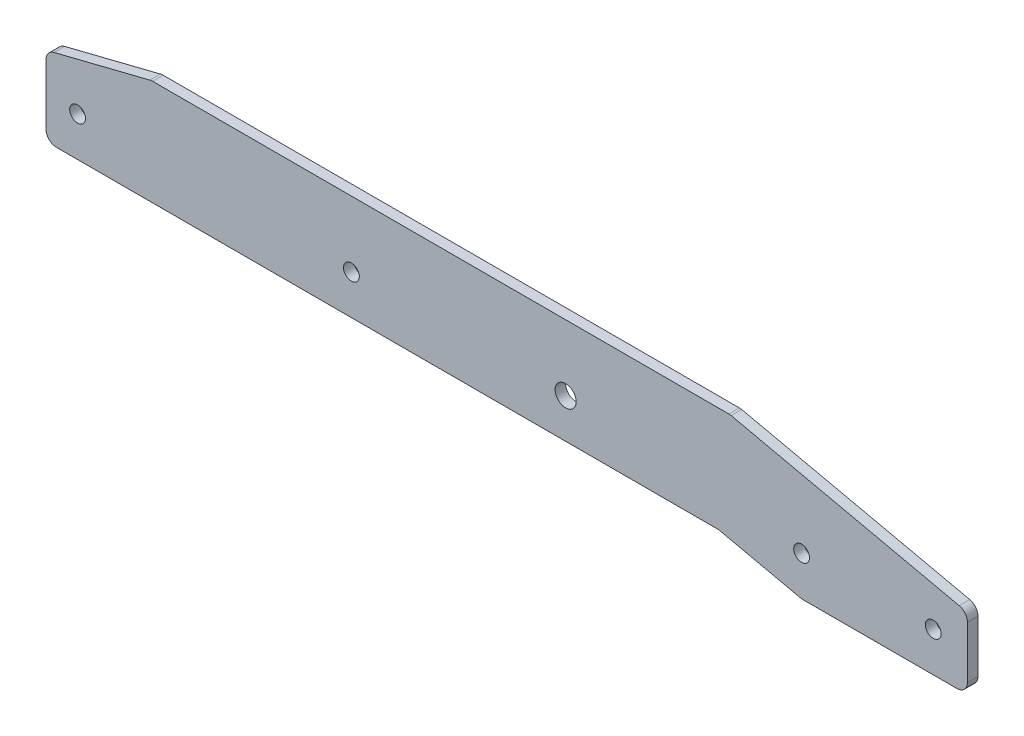
SolidWorks part; units mm, degrees
ref_plane "Спереди" through (0, 0, 0) normal (0, 0, 1) x (1, 0, 0)
ref_plane "Сверху" through (0, 0, 0) normal (0, 1, 0) x (1, 0, 0)
ref_plane "Справа" through (0, 0, 0) normal (1, 0, 0) x (0, 0, -1)
sketch "эскиз" plane through (0, 0, 0) normal (0, 0, 1) x (1, 0, 0)
  line L0 (116.6288, -120) -> (116.6288, -34) construction
  line L1 (-31.3712, -120) -> (-31.3712, -37.5) construction
  line L2 (-163.3712, -34) -> (-129.3712, -34) construction
  line L3 (-163.3712, -120) -> (-31.3712, -120) construction
  line L4 (-163.3712, -34) -> (-181.3712, -34) construction
  line L5 (-31.3712, -120) -> (116.6288, -120) construction
  line L6 (-163.3712, -120) -> (-163.3712, -34) construction
  line L7 (82.6288, -34) -> (116.6288, -34) construction
  line L8 (134.6288, -34) -> (116.6288, -34) construction
  line L9 (-43.8712, -37.5) -> (-18.8712, -37.5) construction
  line L10 (-163.3712, -34) -> (-88.6867, -34) construction
  line L11 (-88.6867, -34) -> (-31.3712, -37.5) construction
  line L12 (-88.6867, -34) -> (0, 0) construction
  line L13 (0, 0) -> (116.6288, -34) construction
  line L14 (-88.6867, -34) -> (-88.6867, 2) construction
  circle A0 centre (-163.3712, -120) radius 57.5 construction
  circle A1 centre (-31.3712, -120) radius 57.5 construction
  circle A2 centre (116.6288, -120) radius 57.5 construction
  circle A3 centre (-181.3712, -34) radius 1.5 construction
  circle A4 centre (-129.3712, -34) radius 1.5 construction
  circle A5 centre (82.6288, -34) radius 1.5 construction
  circle A6 centre (134.6288, -34) radius 1.5 construction
  circle A7 centre (-43.8712, -37.5) radius 1.5 construction
  circle A8 centre (-18.8712, -37.5) radius 1.5 construction
  circle A9 centre (-88.6867, -3) radius 1.5
  circle A10 centre (-88.6867, -13) radius 1.5
  point P31 (-146.3712, -34)
  dimension "D1" = 115
  dimension "D4" = 3
  dimension "D7" = 25
  dimension "D12" = 3
  dimension "D2" = 132
  dimension "D3" = 86
  dimension "D5" = 18
  dimension "D6" = 34
  dimension "D9" = 280
  dimension "D10" = 82.5
  dimension "D11" = 36
  dimension "D13" = 10
  dimension "D14" = 5
  dimension "D15" = 120
sketch "эскиз 1" plane through (0, 0, 0) normal (0, 0, 1) x (1, 0, 0)
  line L0 (-187.3712, -21.5) -> (-187.3712, -41.5)
  line L1 (-187.3712, -41.5) -> (-108.8339, -41.5)
  line L2 (-108.8339, -41.5) -> (-59.6529, -41.5)
  line L3 (-59.6529, -41.5) -> (-43.8712, -45)
  line L4 (-43.8712, -45) -> (-12.3712, -45)
  line L5 (-12.3712, -45) -> (-12.3712, -31.5)
  line L6 (-163.3712, -34) -> (-88.6867, -34) construction
  line L7 (-12.3712, -31.5) -> (-57.4618, -21.5)
  line L8 (-57.4618, -21.5) -> (-110.0582, -21.5)
  line L9 (-110.0582, -21.5) -> (-187.3712, -21.5)
  line L10 (-12.3712, -35) -> (-55.1438, -35) construction
  line L11 (-187.3712, -34) -> (-129.3712, -34) construction
  line L12 (-129.3712, -34) -> (-70.9255, -31.5) construction
  line L13 (-70.9255, -31.5) -> (-43.8712, -37.5) construction
  line L14 (-43.8712, -37.5) -> (-5.3712, -37.5) construction
  line L15 (-163.3712, -34) -> (-129.3712, -34) construction
  line L16 (-43.8712, -37.5) -> (-18.8712, -37.5) construction
  line L17 (-163.3712, -120) -> (-163.3712, -34) construction
  line L20 (-187.3712, -31.5) -> (-109.029, -31.5) construction
  dimension "D1" = 24
  dimension "D2" = 7.5
  dimension "D3" = 20
  dimension "D4" = 19
  dimension "D5" = 20
  dimension "D6" = 2.5
  dimension "D7" = 2.5
  dimension "D8" = 10
extrude "тело маленькой арки" add sketch "эскиз 1" along normal blind 2
sketch "Эскиз1" [suppressed] plane through (0, 0, 0) normal (0, 0, 1) x (1, 0, 0)
  line L0 (40, 10) -> (83.152, -21.5)
  line L1 (83.152, -21.5) -> (141.6288, -21.5)
  line L2 (141.6288, -21.5) -> (141.6288, -41.5)
  line L3 (141.6288, -41.5) -> (76.6288, -41.5)
  line L4 (76.6288, -41.5) -> (33.4768, -10)
  line L5 (33.4768, -10) -> (-10, -10)
  line L6 (-97.6867, -10) -> (-97.6867, 10)
  line L7 (-10, -10) -> (-10, 29.5)
  line L8 (-97.6867, 0) -> (0, 0) construction
  line L9 (0, 0) -> (46.5768, -34) construction
  line L10 (46.5768, -34) -> (141.6288, -34) construction
  line L11 (116.6288, -120) -> (116.6288, -34) construction
  line L12 (82.6288, -34) -> (116.6288, -34) construction
  line L13 (141.6288, -31.5) -> (43.152, -31.5) construction
  line L14 (134.6288, -34) -> (116.6288, -34) construction
  line L15 (-97.6867, -10) -> (-97.6867, -18)
  line L16 (-97.6867, -18) -> (-79.6867, -18)
  line L17 (-79.6867, -18) -> (-79.6867, -0.2843)
  line L18 (-88.6867, 4.8579) -> (-88.6867, -18) construction
  line L19 (-88.6867, -34) -> (-88.6867, 2) construction
  line L20 (0, 0) -> (0, 39.5) construction
  line L21 (-10, 29.5) -> (-49.9025, 29.5)
  line L22 (-49.9025, 29.5) -> (-79.6867, -0.2843)
  line L23 (40, 10) -> (10, 10)
  line L24 (10, 10) -> (10, 49.5)
  line L25 (10, 49.5) -> (-58.1867, 49.5)
  line L26 (-58.1867, 49.5) -> (-97.6867, 10)
  line L27 (0, 39.5) -> (-54.0446, 39.5) construction
  line L28 (-54.0446, 39.5) -> (-88.6867, 4.8579) construction
  point P29 (-88.6867, -18)
  dimension "D1" = 20
  dimension "D2" = 25
  dimension "D3" = 40
  dimension "D4" = 20
  dimension "D5" = 10
  dimension "D6" = 2.5
  dimension "D7" = 88.6867
  dimension "D8" = 9
  dimension "D9" = 5
  dimension "D10" = 39.5
  dimension "D11" = 10
  dimension "D12" = 10
  dimension "D13" = 10
  dimension "D14" = 10
  dimension "D15" = 135
  dimension "D16" = 10
  dimension "D17" = 20
  dimension "D18" = 30
extrude "тело большой арки" [suppressed] add sketch "Эскиз1" along normal blind 2
sketch "Эскиз2" plane through (0, 0, 2) normal (0, 0, 1) x (1, 0, 0)
  circle A0 centre (-181.3712, -34) radius 1.5
  circle A1 centre (-129.3712, -34) radius 1.5
  dimension "D1" = 3
extrude "крепление сервы" cut sketch "Эскиз2" against normal through all
sketch "Эскиз3" plane through (0, 0, 2) normal (0, 0, 1) x (1, 0, 0)
  circle A0 centre (-43.8712, -37.5) radius 1.5
  circle A1 centre (-18.8712, -37.5) radius 1.5
  dimension "D1" = 3
extrude "крепление неподвижного колеса" cut sketch "Эскиз3" against normal through all
sketch "Эскиз4" plane through (0, 0, 2) normal (0, 0, 1) x (1, 0, 0)
  circle A0 centre (-88.6867, -34) radius 2
  dimension "D1" = 4
extrude "ось вращения маленькой арки" cut sketch "Эскиз4" against normal through all
sketch "Эскиз5" [suppressed] plane through (0, 0, 2) normal (0, 0, 1) x (1, 0, 0)
  circle A0 centre (82.6288, -34) radius 1.5
  circle A1 centre (134.6288, -34) radius 1.5
  dimension "D1" = 3
extrude "крепление сервы к большой арке" [suppressed] cut sketch "Эскиз5" against normal through all
sketch "Эскиз6" [suppressed] plane through (0, 0, 2) normal (0, 0, 1) x (1, 0, 0)
  circle A0 centre (0, 0) radius 5.5
  dimension "D1" = 11
extrude "ось вращения большой арки" [suppressed] cut sketch "Эскиз6" against normal through all
sketch "Эскиз9" [suppressed] plane through (0, 0, 2) normal (0, 0, 1) x (1, 0, 0)
  circle A0 centre (-88.6867, -3) radius 1.5
  circle A1 centre (-88.6867, -13) radius 1.5
  dimension "D1" = 3
extrude "крепление к маленькой арке" [suppressed] cut sketch "Эскиз9" against normal through all
sketch "Эскиз13" [suppressed] plane through (0, 0, 2) normal (0, 0, 1) x (1, 0, 0)
  line L0 (33.4768, -10) -> (40, 10) construction
  line L1 (83.152, -21.5) -> (71.36, -37.6539) construction
  line L3 (33.4768, -10) -> (76.6288, -41.5) construction
  line L5 (83.152, -21.5) -> (40, 10) construction
  line L8 (77.256, -29.577) -> (36.7384, 0) construction
  line L9 (36.7384, 0) -> (0, 0) construction
  line L10 (20.9607, 0) -> (49.482, -9.3025) construction
  circle A0 centre (20.9607, 0) radius 1.5
  circle A1 centre (49.482, -9.3025) radius 1.5
  point P15 (35.2213, -4.6513)
  dimension "D1" = 3
  dimension "D2" = 30
extrude "отверстия для ребра сзади" [suppressed] cut sketch "Эскиз13" against normal through all
sketch "Эскиз14" [suppressed] plane through (0, 0, 2) normal (0, 0, 1) x (1, 0, 0)
  line L2 (0, 39.5) -> (0, 0) construction
  circle A0 centre (0, 39.5) radius 2
  dimension "D1" = 4
  dimension "D2" = 39.5
extrude "отверстие для тяга" [suppressed] cut sketch "Эскиз14" against normal through all
sketch "Эскиз18" [suppressed] plane through (0, 0, 2) normal (0, 0, 1) x (1, 0, 0)
  line L0 (-79.6867, -0.2843) -> (-93.8289, 13.8579) construction
  line L1 (-58.1867, 49.5) -> (-97.6867, 10) construction
  line L4 (-79.6867, -0.2843) -> (-49.9025, 29.5) construction
  line L5 (-49.9025, 29.5) -> (-58.1867, 49.5) construction
  line L6 (-10, 29.5) -> (-10, 49.5) construction
  line L7 (10, 49.5) -> (-58.1867, 49.5) construction
  line L8 (-86.7578, 6.7868) -> (-54.0446, 39.5) construction
  line L9 (-54.0446, 39.5) -> (-10, 39.5) construction
  line L10 (-65.5251, 28.0195) -> (-37.8087, 39.5) construction
  circle A0 centre (-37.8087, 39.5) radius 1.5
  circle A1 centre (-65.5251, 28.0195) radius 1.5
  point P22 (-51.6669, 33.7597)
  dimension "D1" = 3
  dimension "D2" = 30
extrude "отверстия для ребра спереди" [suppressed] cut sketch "Эскиз18" against normal through all
sketch "Эскиз16" [suppressed] plane through (0, 0, 2) normal (0, 0, 1) x (1, 0, 0)
  line L0 (0, 0) -> (-8.6933, 2.3294) construction
  line L1 (0, 0) -> (6.364, 6.364) construction
  line L2 (2.3294, -8.6933) -> (0, 0) construction
  line L3 (-88.6867, -3) -> (-88.6867, -13) construction
  line L4 (-10, 29.5) -> (-10, -10) construction
  circle A0 centre (0, 0) radius 9 construction
  circle A1 centre (-8.6933, 2.3294) radius 1.5
  circle A2 centre (6.364, 6.364) radius 1.5
  circle A3 centre (0, 0) radius 5.5
  circle A4 centre (2.3294, -8.6933) radius 1.5
  dimension "D1" = 18
  dimension "D2" = 3
  dimension "D4" = 120
  dimension "D3" = 11
  dimension "D5" = 45
  dimension "D6" = 120
extrude "крепление большой арки" [suppressed] cut sketch "Эскиз16" against normal through all
sketch "Эскиз19" [suppressed] plane through (0, 0, 2) normal (0, 0, 1) x (1, 0, 0)
  circle A0 centre (-8.6933, 2.3294) radius 1.5
  circle A1 centre (-8.6933, 2.3294) radius 3.5
  circle A2 centre (2.3294, -8.6933) radius 1.5
  circle A3 centre (2.3294, -8.6933) radius 3.5
  arc A4 (3.066, -10) -> (1.5927, -10) centre (2.3294, -8.6933) ccw construction
  arc A5 (-10, 1.5927) -> (-10, 3.066) centre (-8.6933, 2.3294) ccw construction
  dimension "D1" = 7
extrude "наплывы" [suppressed] add sketch "Эскиз19" against normal up to surface (2 mm away) up to face at (-86.6867, -34, 0)
sketch "Эскиз20" [suppressed] plane through (0, 0, 2) normal (0, 0, 1) x (1, 0, 0)
  line L0 (-97.6867, -18) -> (-79.6867, -18) construction
  line L1 (-97.6867, -18) -> (-79.6867, -18)
  line L2 (-97.6867, -18) -> (-97.6867, -21)
  line L3 (-97.6867, -21) -> (-79.6867, -21)
  line L4 (-79.6867, -18) -> (-79.6867, -21)
  dimension "D1" = 3
extrude "стопор" [suppressed] add sketch "Эскиз20" against normal up to surface (2 mm away) up to face at (-86.6867, -34, 0)
sketch "Эскиз21" [suppressed] plane through (0, 0, 2) normal (0, 0, 1) x (1, 0, 0)
  line L0 (-88.6867, -13) -> (-88.6867, -34) construction
  line L2 (-97.6867, -14.3701) -> (-86.9207, -20.5858)
  line L4 (-97.6867, 10) -> (-97.6867, -21) construction
  line L8 (-86.9207, -20.5858) -> (-79.6867, -18.6475)
  line L11 (-79.6867, -21) -> (-79.6867, -0.2843) construction
  line L12 (-88.6867, -34) -> (-111.8135, -20.6478) construction
  line L13 (-88.6867, -34) -> (-66.5235, -28.0614) construction
  line L14 (-97.6867, -14.3701) -> (-97.6867, -21)
  line L15 (-97.6867, -21) -> (-79.6867, -21)
  line L16 (-79.6867, -21) -> (-79.6867, -18.6475)
  dimension "D1" = 12.5
  dimension "D2" = 12.5
  dimension "D3" = 60
  dimension "D4" = 75
extrude "углы стопора" [suppressed] cut sketch "Эскиз21" against normal through all and the other way through all
chamfer "Фаска1" [suppressed] distance 20 angle 45
chamfer "Фаска2" [suppressed] distance 30
chamfer "Фаска5" [suppressed] distance 5 distance2 20
sketch "Эскиз22" [suppressed] plane through (0, 0, 2) normal (0, 0, 1) x (1, 0, 0)
  line L0 (10, 40) -> (0.5, 49.5)
  line L1 (10, 49.5) -> (-58.1867, 49.5) construction
  line L2 (40, 10) -> (10, 40) construction
  line L3 (0.5, 49.5) -> (10, 49.5)
  line L4 (10, 49.5) -> (10, 40)
extrude "Вырез-Вытянуть2" [suppressed] cut sketch "Эскиз22" against normal through all
fillet "Скругление10" [suppressed] radius 2
fillet "Скругление11" [suppressed] radius 10
fillet "Скругление12" [suppressed] radius 7
fillet "Скругление13" [suppressed] radius 1
chamfer "Фаска4" distance 20 distance2 5 1 edges at (-187.3712, -21.5, 1) first distance on face at (-122.4165, -21.5, 1)
fillet "Скругление12 маленькой арки" radius 2 8 edges at (-12.3712, -45, 1) (-187.3712, -41.5, 1) (-43.8712, -45, 1) (-59.6529, -41.5, 1) (-57.4618, -21.5, 1) (-167.3712, -21.5, 1) (-187.3712, -26.5, 1) (-12.3712, -31.5, 1)
